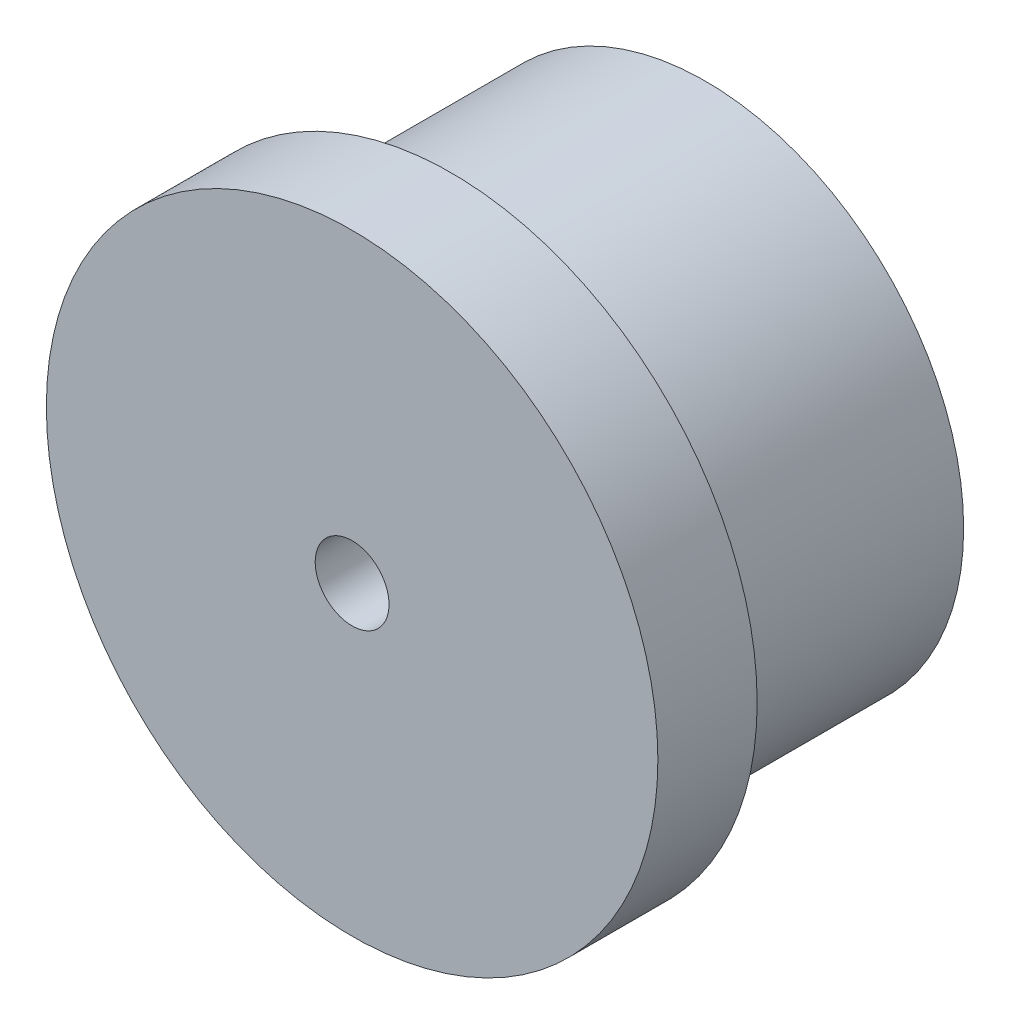
SolidWorks part; units mm, degrees
material "Nylon 101"
ref_plane "Front Plane" through (0, 0, 0) normal (0, 0, 1) x (1, 0, 0)
ref_plane "Top Plane" through (0, 0, 0) normal (0, 1, 0) x (1, 0, 0)
ref_plane "Right Plane" through (0, 0, 0) normal (1, 0, 0) x (0, 0, -1)
sketch "Sketch1" plane through (0, 0, 0) normal (0, 0, 1) x (1, 0, 0)
  circle A0 centre (6.731, -165.7192) radius 4.1275
  dimension "D1" = 8.255
extrude "Boss-Extrude2" add sketch "Sketch1" against normal blind 4.064
sketch "Sketch2" plane through (0, 0, 0) normal (0, 0, 1) x (1, 0, 0)
  circle A2 centre (6.731, -165.7192) radius 4.8895
  circle A3 centre (6.731, -165.7192) radius 4.8895
  dimension "D1" = 0.762
extrude "Boss-Extrude3" add sketch "Sketch2" along normal blind 1.5875
sketch "Sketch3" plane through (0, 0, 1.5875) normal (0, 0, 1) x (1, 0, 0)
  circle A0 centre (6.731, -165.7192) radius 0.635
  dimension "D1" = 1.27
split line "Split Line1" [suppressed]
dome "Dome1" [suppressed] faces to dome 1 distance 0.635 parameters "D1"=0.635
hole_wizard "#56 (0.0465) Diameter Hole1" positions "Sketch5" profile "Sketch4" hole size "#56" standard "ANSI Inch" end condition through all
sketch "Sketch5" plane through (0, 0, -4.064) normal (0, 0, -1) x (-1, 0, 0)
  point P0 (-6.731, -165.7192)
sketch "Sketch4" plane through (6.731, -165.7192, -4.064) normal (1, 0, 0) x (0, 1, 0)
  line L0 (0, 0) -> (0, 5.6515)
  line L1 (0, 5.6515) -> (0.5905, 5.6515)
  line L2 (0.5905, 5.6515) -> (0.5905, 0)
  line L5 (0.5905, 0) -> (0, 0)
  line L11 (0, -6.35) -> (0, 107.95) construction
  dimension "Thru Hole Dia." = 1.1811
  dimension "Thru Hole Depth" = 5.6515
